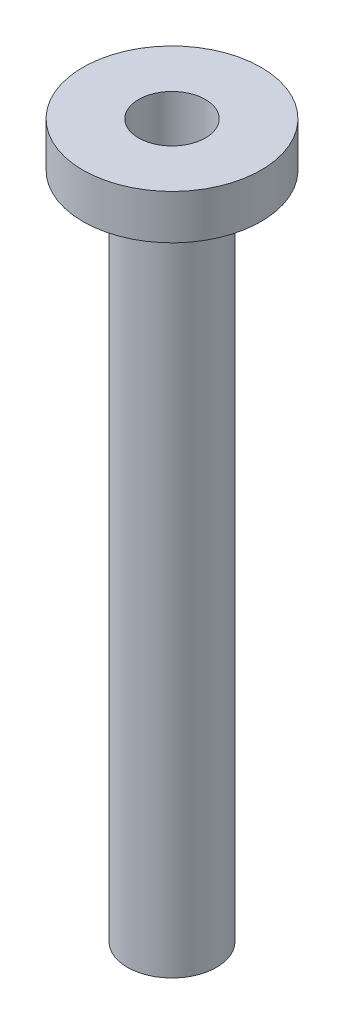
SolidWorks part; units mm, degrees
ref_plane "Front Plane" through (0, 0, 0) normal (0, 0, 1) x (1, 0, 0)
ref_plane "Top Plane" through (0, 0, 0) normal (0, 1, 0) x (1, 0, 0)
ref_plane "Right Plane" through (0, 0, 0) normal (1, 0, 0) x (0, 0, -1)
sketch "Sketch1" plane through (0, 0, 0) normal (0, 0, 1) x (1, 0, 0)
  line L0 (0, 0) -> (0, -101.6)
  line L3 (0, -101.6) -> (-6.35, -101.6)
  line L4 (-6.35, -101.6) -> (-6.35, -6.35)
  line L5 (-6.35, -6.35) -> (-12.7, -6.35)
  line L6 (-12.7, -6.35) -> (-12.7, 0)
  line L7 (-12.7, 0) -> (0, 0)
  point P1 (0, 2.4392)
  point P2 (0, -46.3791)
  point P3 (0, 0)
  dimension "D1" = 6.35
  dimension "D2" = 6.35
  dimension "D3" = 6.35
  dimension "D4" = 101.6
revolve "Revolve1" add sketch "Sketch1" angle 360 about L0
hole_wizard "3/8 (0.375) Diameter Hole1" positions "Sketch2" profile "Sketch4" hole size "3/8" standard "ANSI Inch"
sketch "Sketch2" plane through (0, 0, 0) normal (0, 1, 0) x (1, 0, 0)
  point P0 (0, 0)
sketch "Sketch4" plane through (0, 0, 0) normal (1, 0, 0) x (0, 0, 1)
  line L0 (0, 0) -> (0, 98.1116)
  line L1 (0, 98.1116) -> (4.7625, 95.25)
  line L2 (4.7625, 95.25) -> (4.7625, 0)
  line L5 (4.7625, 0) -> (0, 0)
  line L10 (0, 98.1116) -> (-4.7625, 95.25) construction
  line L11 (0, -6.35) -> (0, 107.95) construction
  dimension "Hole Dia." = 9.525
  dimension "Hole Depth" = 95.25
  dimension "Drill Angle" = 118
